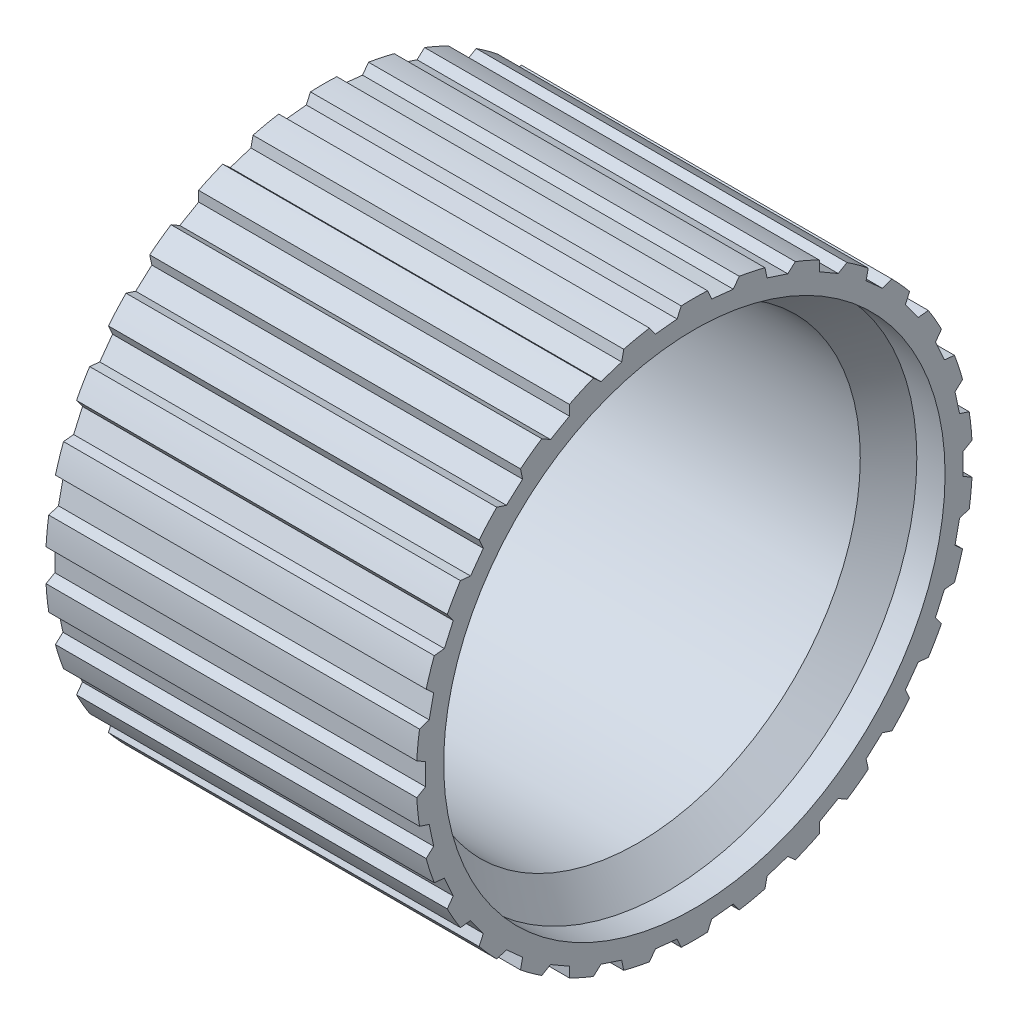
SolidWorks part; units mm, degrees
ref_plane "Front Plane" through (0, 0, 0) normal (0, 0, 1) x (1, 0, 0)
ref_plane "Top Plane" through (0, 0, 0) normal (0, 1, 0) x (1, 0, 0)
ref_plane "Right Plane" through (0, 0, 0) normal (1, 0, 0) x (0, 0, -1)
sketch "Sketch1" plane through (0, 0, 0) normal (0, 0, 1) x (1, 0, 0)
  line L0 (-20, 30) -> (20, 30)
  line L1 (-20, 30) -> (-20, 27.05)
  line L2 (-20, 27.05) -> (-16.95, 27.05)
  line L3 (-16.95, 27.05) -> (-16.95, 24)
  line L4 (-16.95, 24) -> (13.9, 24)
  line L5 (13.9, 24) -> (16.95, 27.05)
  line L6 (16.95, 27.05) -> (20, 27.05)
  line L7 (20, 27.05) -> (20, 30)
  point P2 (0, 30)
  dimension "D2" = 3.05
  dimension "D1" = 20
  dimension "D3" = 3.05
  dimension "D4" = 3.05
  dimension "D5" = 3.05
  dimension "D6" = 30
  dimension "D7" = 3.05
  dimension "D8" = 6
ref_axis "Axis1" through (22, 0, 0) along (-1, 0, 0)
revolve "Revolve1" add sketch "Sketch1" angle 360 about axis through (22, 0, 0) along (-1, 0, 0)
sketch "Sketch2" plane through (0, 0, 0) normal (0, 0, 1) x (1, 0, 0)
  line L0 (-20, 30) -> (20, 30)
  dimension "D1" = 30
surface "Surface-Revolve1" sketch "Sketch2" parameters "D1"=360
ref_plane "Plane1" through (0, 0, 117) normal (0, 0, 1) x (1, 0, 0)
delete or keep bodies "Body-Delete/Keep 1" type delete bodies bodies 102
sketch "Sketch6" plane through (0, 0, 0) normal (1, 0, 0) x (0, 0, -1)
  line L0 (0, 0) -> (-30, 0) construction
  line L1 (-30, 1.75) -> (-29, 1.1726)
  line L2 (-29, 1.1726) -> (-29, -1.1726)
  line L3 (-29, -1.1726) -> (-30, -1.75)
  line L4 (-30, -1.75) -> (-30, 1.75)
  circle A0 centre (0, 0) radius 30 construction
  point P8 (-29, 0)
  dimension "D1" = 1
  dimension "D2" = 60
  dimension "D3" = 60
  dimension "D4" = 3.5
extrude "Cut-Extrude2" cut sketch "Sketch6" against normal through all both and the other way through all
pattern_circular "CirPattern4" count 30 over 360 about axis through (0, 0, 0) along (1, 0, 0) of "Cut-Extrude2"
equation "\"D1@Sketch8\"=\"D2@Sketch8\"+6"
